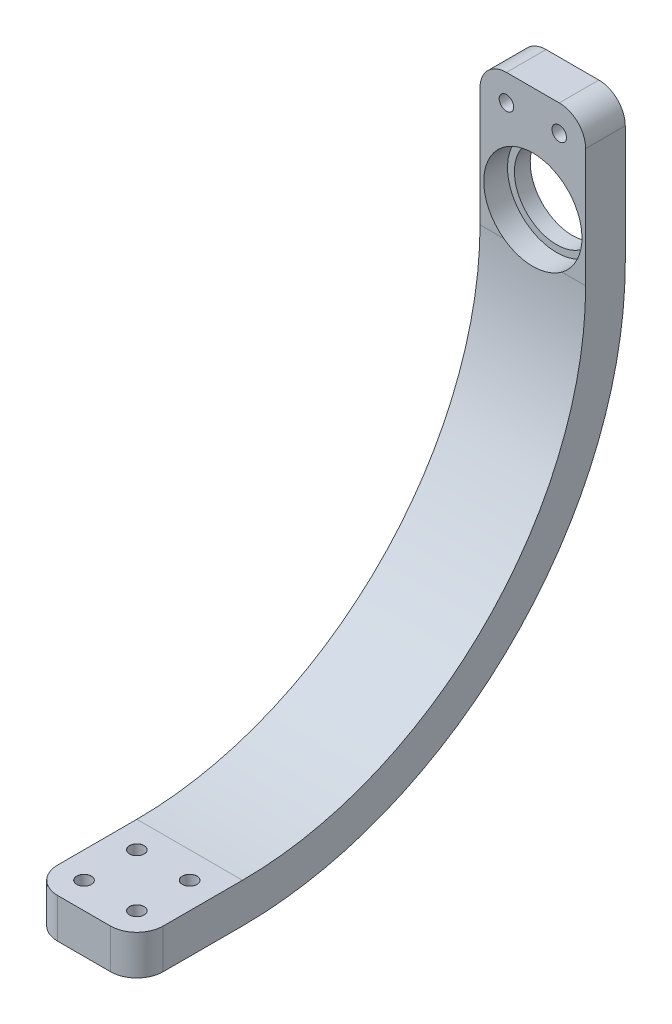
SolidWorks part; units mm, degrees
ref_plane "Front Plane" through (0, 0, 0) normal (0, 0, 1) x (1, 0, 0)
ref_plane "Top Plane" through (0, 0, 0) normal (0, 1, 0) x (1, 0, 0)
ref_plane "Right Plane" through (0, 0, 0) normal (1, 0, 0) x (0, 0, -1)
sketch "Sketch6" plane through (0, 0, 0) normal (1, 0, 0) x (0, 0, -1)
  line L0 (0, 0) -> (40, 0)
  line L1 (0, 0) -> (0, 15)
  line L2 (0, 15) -> (40, 15)
  line L3 (170, 145) -> (170, 200)
  line L4 (170, 200) -> (185, 200)
  line L5 (185, 200) -> (185, 145)
  arc A0 (40, 15) -> (170, 145) centre (40, 145) ccw
  arc A1 (40, 0) -> (185, 145) centre (40, 145) ccw
  dimension "D3" = 185
  dimension "D1" = 15
  dimension "D2" = 40
  dimension "D4" = 200
extrude "Boss-Extrude2" add sketch "Sketch6" along normal blind 40
sketch "Sketch9" plane through (0, 15, 0) normal (0, 1, 0) x (1, 0, 0)
  line L0 (10, 30) -> (30, 30) construction
  line L1 (30, 30) -> (30, 10) construction
  line L2 (30, 10) -> (10, 10) construction
  line L3 (10, 10) -> (10, 30) construction
  line L5 (40, 0) -> (0, 0) construction
  line L6 (40, 40) -> (40, 0) construction
  point P0 (10, 30)
  point P2 (30, 30)
  point P4 (10, 10)
  point P6 (30, 10)
  point P21 (20, 0)
  point P22 (20, 10)
  point P25 (40, 20)
  point P26 (30, 20)
  dimension "D1" = 20
hole_wizard "M5 Clearance Hole2" positions "Sketch9" profile "Sketch8" hole size "M5" standard "ANSI Metric" end condition through all
sketch "Sketch8" plane through (10, 15, -30) normal (1, 0, 0) x (0, 0, 1)
  line L0 (0, 0) -> (0, 15)
  line L1 (0, 15) -> (2.75, 15)
  line L2 (2.75, 15) -> (2.75, 0.025)
  line L3 (2.75, 0.025) -> (2.775, 0)
  line L5 (2.775, 0) -> (0, 0)
  line L6 (-2.75, 0.025) -> (-2.775, 0) construction
  line L11 (0, -6.35) -> (0, 107.95) construction
  dimension "Thru Hole Dia." = 5.5
  dimension "Thru Hole Depth" = 15
  dimension "Near C'Sink Dia." = 5.55
  dimension "Near C'Sink Angle" = 90
sketch "Sketch10" plane through (0, 0, -185) normal (0, 0, -1) x (-1, 0, 0)
  line L0 (-40, 200) -> (0, 200) construction
  circle A0 centre (-20, 160) radius 16
  point P4 (-20, 200)
  dimension "D2" = 32
  dimension "D1" = 40
extrude "Cut-Extrude1" cut sketch "Sketch10" against normal up to next
sketch "Sketch12" plane through (0, 0, -170) normal (0, 0, 1) x (1, 0, 0)
  circle A0 centre (20, 160) radius 18.6
  dimension "D1" = 37.2
extrude "Cut-Extrude2" cut sketch "Sketch12" against normal blind 9 and the other way blind 10
fillet "Fillet1" radius 10 4 edges at (40, 7.5, 0) (0, 7.5, 0) (40, 200, -177.5) (0, 200, -177.5) first distance on face at (40, 82.8807, -105.8693) first distance on face at (0, 82.8807, -105.8693)
sketch "Sketch15" plane through (0, 0, -185) normal (0, 0, -1) x (-1, 0, 0)
  line L0 (-30, 190) -> (-10, 190) construction
  line L2 (-30, 200) -> (-10, 200) construction
  circle A0 centre (-20, 160) radius 16 construction
  point P0 (-30, 190)
  point P2 (-10, 190)
  point P10 (-20, 200)
  point P11 (-20, 190)
  dimension "D1" = 30
  dimension "D2" = 20
hole_wizard "M5 Clearance Hole3" positions "Sketch15" profile "Sketch14" hole size "M5" standard "ANSI Metric" end condition through all
sketch "Sketch14" plane through (30, 190, -185) normal (1, 0, 0) x (0, 1, 0)
  line L0 (0, 0) -> (0, 185.5637)
  line L1 (0, 185.5637) -> (2.75, 185.5637)
  line L2 (2.75, 185.5637) -> (2.75, 0.025)
  line L3 (2.75, 0.025) -> (2.775, 0)
  line L5 (2.775, 0) -> (0, 0)
  line L6 (-2.75, 0.025) -> (-2.775, 0) construction
  line L11 (0, -6.35) -> (0, 107.95) construction
  dimension "Thru Hole Dia." = 5.5
  dimension "Thru Hole Depth" = 185.5637
  dimension "Near C'Sink Dia." = 5.55
  dimension "Near C'Sink Angle" = 90
